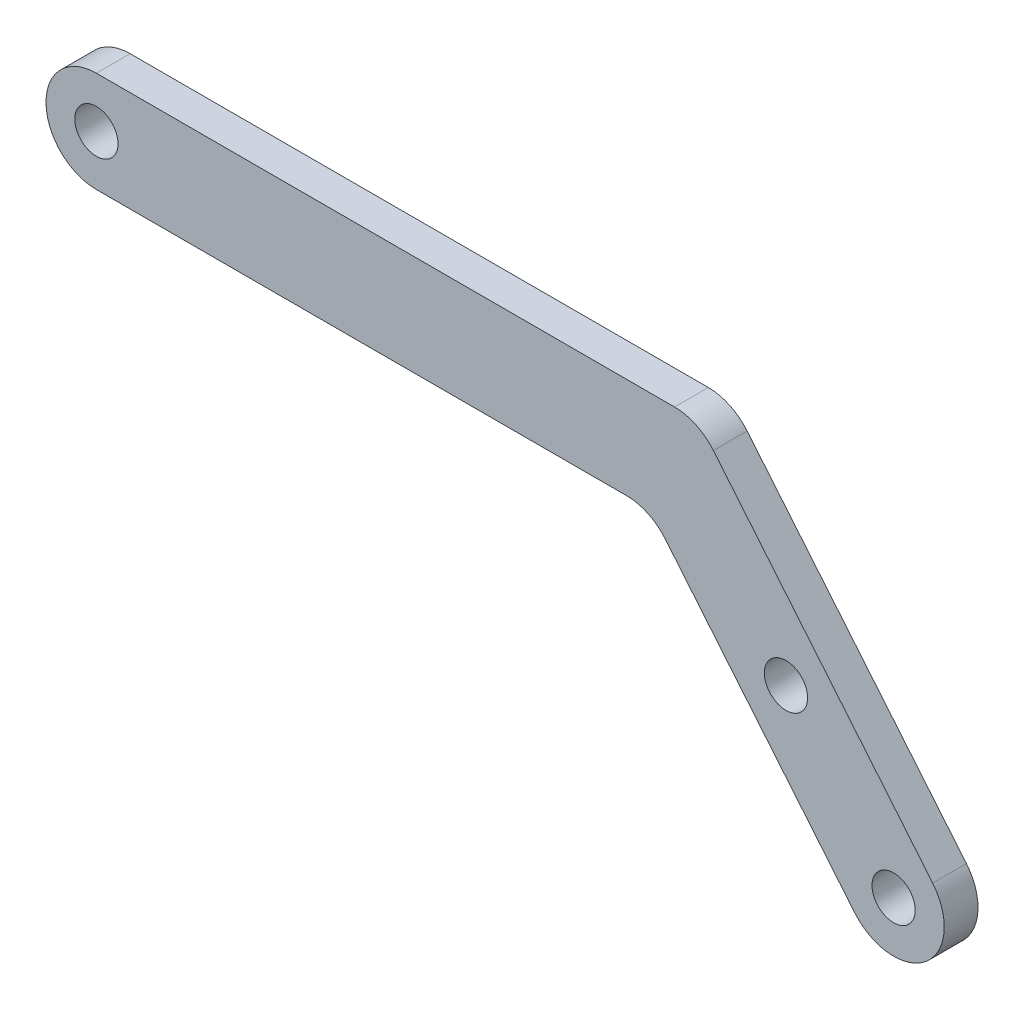
SolidWorks part; units mm, degrees
ref_plane "Front Plane" through (0, 0, 0) normal (0, 0, 1) x (1, 0, 0)
ref_plane "Top Plane" through (0, 0, 0) normal (0, 1, 0) x (1, 0, 0)
ref_plane "Right Plane" through (0, 0, 0) normal (1, 0, 0) x (0, 0, -1)
sketch "Sketch1" plane through (0, 0, 0) normal (0, 0, 1) x (1, 0, 0)
  line L0 (-64.8477, 17.4379) -> (-10.4775, 17.4379)
  line L1 (-6.8273, 15.7206) -> (13.79, -9.1942)
  line L2 (6.4517, -15.2667) -> (-11.3492, 6.2447)
  line L3 (-14.9995, 7.9621) -> (-64.8477, 7.9621)
  line L4 (0, 0) -> (10.1208, -12.2305) construction
  circle A0 centre (0, 0) radius 2.032
  circle A1 centre (-64.8477, 12.7) radius 2.032
  arc A2 (-64.8477, 17.4379) -> (-64.8477, 7.9621) centre (-64.8477, 12.7) ccw
  arc A4 (-11.3492, 6.2447) -> (-14.9995, 7.9621) centre (-14.9995, 3.2241) ccw
  arc A5 (-6.8273, 15.7206) -> (-10.4775, 17.4379) centre (-10.4775, 12.7) ccw
  circle A6 centre (10.1208, -12.2305) radius 2.032
  arc A7 (6.4517, -15.2667) -> (13.79, -9.1942) centre (10.1208, -12.2305) ccw
  point P14 (11.8814, -6.9739)
  point P19 (4.8277, -13.2832)
  dimension "D1" = 66.0796
  dimension "D2" = 4.064
  dimension "D3" = 15.875
  dimension "D4" = 12.7
  dimension "D7" = 9.525
  dimension "D5" = 10.4775
  dimension "D6" = 12.7
extrude "Boss-Extrude1" add sketch "Sketch1" along normal blind 3.175
